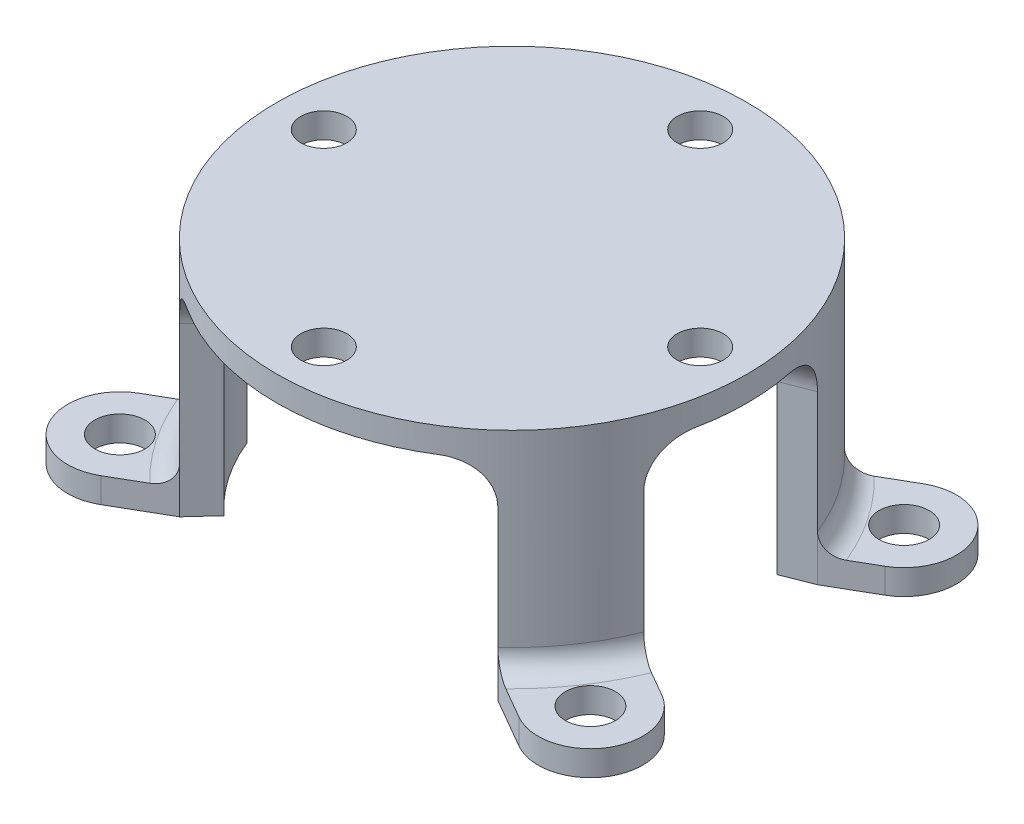
SolidWorks part; units mm, degrees
ref_plane "Front Plane" through (0, 0, 0) normal (0, 0, 1) x (1, 0, 0)
ref_plane "Top Plane" through (0, 0, 0) normal (0, 1, 0) x (1, 0, 0)
ref_plane "Right Plane" through (0, 0, 0) normal (1, 0, 0) x (0, 0, -1)
sketch "Sketch2" plane through (0, 0, 0) normal (0, 1, 0) x (1, 0, 0)
  circle A0 centre (0, 0) radius 22.5
  dimension "D1" = 45
extrude "Boss-Extrude1" add sketch "Sketch2" along normal blind 2.4
sketch "Sketch3" plane through (0, 0, 0) normal (0, 1, 0) x (1, 0, 0)
  circle A0 centre (0, 18) radius 2.2
  circle A1 centre (18, 0) radius 2.2
  circle A2 centre (0, -18) radius 2.2
  circle A3 centre (-18, 0) radius 2.2
  point P2 (0, 0)
  point P12 (0, 0)
  dimension "D1" = 4.4
  dimension "D2" = 18
  dimension "D4" = 18
  dimension "D3" = 4
extrude "Cut-Extrude1" cut sketch "Sketch3" against normal up to surface from surface up to face at (0, 0, 22.5) starting at face at (0, 2.4, 22.5)
sketch "Sketch4" plane through (0, 0, 0) normal (0, 1, 0) x (1, 0, 0)
  line L0 (0, 0) -> (-22.5, 0) construction
  line L1 (0, -1.32) -> (0, 1.32) construction
  line L2 (-25, 10.6699) -> (-20.9098, 8.3084)
  line L3 (-20, 19.3301) -> (-15.2205, 16.5707)
  line L4 (-25, -10.6699) -> (-20.9098, -8.3084)
  line L5 (-20, -19.3301) -> (-15.2205, -16.5707)
  line L6 (20, -19.3301) -> (15.2205, -16.5707)
  line L7 (25, -10.6699) -> (20.9098, -8.3084)
  line L8 (25, 10.6699) -> (20.9098, 8.3084)
  line L9 (20, 19.3301) -> (15.2205, 16.5707)
  circle A0 centre (-22.5, 15) radius 2.4
  circle A1 centre (-22.5, -15) radius 2.4
  circle A2 centre (22.5, -15) radius 2.4
  circle A3 centre (22.5, 15) radius 2.4
  arc A4 (-20, 19.3301) -> (-25, 10.6699) centre (-22.5, 15) ccw
  arc A5 (25, 10.6699) -> (20, 19.3301) centre (22.5, 15) ccw
  arc A6 (20, -19.3301) -> (25, -10.6699) centre (22.5, -15) ccw
  arc A7 (-25, -10.6699) -> (-20, -19.3301) centre (-22.5, -15) ccw
  circle A8 centre (0, 0) radius 22.5 construction
  arc A9 (-15.2205, 16.5707) -> (-20.9098, 8.3084) centre (0, 0) ccw
  arc A10 (20.9098, 8.3084) -> (15.2205, 16.5707) centre (0, 0) ccw
  arc A11 (15.2205, -16.5707) -> (20.9098, -8.3084) centre (0, 0) ccw
  arc A12 (-20.9098, -8.3084) -> (-15.2205, -16.5707) centre (0, 0) ccw
  point P7 (0, 0)
  point P8 (0, 0)
  point P9 (0, 0)
  point P19 (0, 0)
  dimension "D1" = 4.8
  dimension "D4" = 4.8
  dimension "D6" = 10
  dimension "D9" = 10
  dimension "D3" = 15
  dimension "D5" = 15
  dimension "D2" = 22.5
  dimension "D10" = 30
  dimension "D11" = 30
extrude "Boss-Extrude2" add sketch "Sketch4" along normal blind 2.4 from offset 20 separate body offset against normal yes
sketch "Sketch5" plane through (0, 0, 0) normal (0, 1, 0) x (1, 0, 0)
  line L0 (-20.9098, 8.3084) -> (-18.1218, 7.2006)
  line L1 (-15.2205, 16.5707) -> (-13.1911, 14.3612)
  line L2 (15.2205, 16.5707) -> (13.1911, 14.3612)
  line L3 (20.9098, 8.3084) -> (18.1218, 7.2006)
  line L4 (20.9098, -8.3084) -> (18.1218, -7.2006)
  line L5 (15.2205, -16.5707) -> (13.1911, -14.3612)
  line L6 (-15.2205, -16.5707) -> (-13.1911, -14.3612)
  line L7 (-20.9098, -8.3084) -> (-18.1218, -7.2006)
  arc A0 (-20.9098, -8.3084) -> (-15.2205, -16.5707) centre (0, 0) ccw construction
  arc A1 (15.2205, -16.5707) -> (20.9098, -8.3084) centre (0, 0) ccw construction
  arc A2 (20.9098, 8.3084) -> (15.2205, 16.5707) centre (0, 0) ccw construction
  arc A3 (-15.2205, 16.5707) -> (-20.9098, 8.3084) centre (0, 0) ccw construction
  arc A4 (-20.9098, -8.3084) -> (-15.2205, -16.5707) centre (0, 0) ccw
  arc A5 (15.2205, -16.5707) -> (20.9098, -8.3084) centre (0, 0) ccw
  arc A6 (20.9098, 8.3084) -> (15.2205, 16.5707) centre (0, 0) ccw
  arc A7 (-15.2205, 16.5707) -> (-20.9098, 8.3084) centre (0, 0) ccw
  arc A8 (-13.1911, 14.3612) -> (-18.1218, 7.2006) centre (0, 0) ccw
  arc A9 (18.1218, 7.2006) -> (13.1911, 14.3612) centre (0, 0) ccw
  arc A10 (13.1911, -14.3612) -> (18.1218, -7.2006) centre (0, 0) ccw
  arc A11 (-18.1218, -7.2006) -> (-13.1911, -14.3612) centre (0, 0) ccw
  dimension "D1" = 3
extrude "Boss-Extrude3" add sketch "Sketch5" along normal up to surface from surface up to face at (0, 0, -15.8) starting at face at (-21.4817, -20, 14.425)
fillet "Fillet1" radius 4 11 edges at (14.2058, 0, 15.466) (16.0606, 0, 11.0592) (19.5158, 0, 7.7545) (19.5158, 0, -7.7545) (-14.2058, 0, 15.466) (-16.0606, 0, 11.0592) (-14.2058, 0, -15.466) (14.2058, 0, -15.466) (16.0606, 0, -11.0592) (-19.5158, 0, -7.7545) (-16.0606, 0, -11.0592)
fillet "Fillet2" radius 2 4 edges at (-18.5315, -17.6, 12.7607) (18.5315, -17.6, 12.7607) (-18.5315, -17.6, -12.7607) (18.5315, -17.6, -12.7607)
equation "\"D4@Sketch4\"=\"D1@Sketch4\""
equation "\"D5@Sketch4\"=\"D3@Sketch4\""
equation "\"D9@Sketch4\"=\"D6@Sketch4\""
